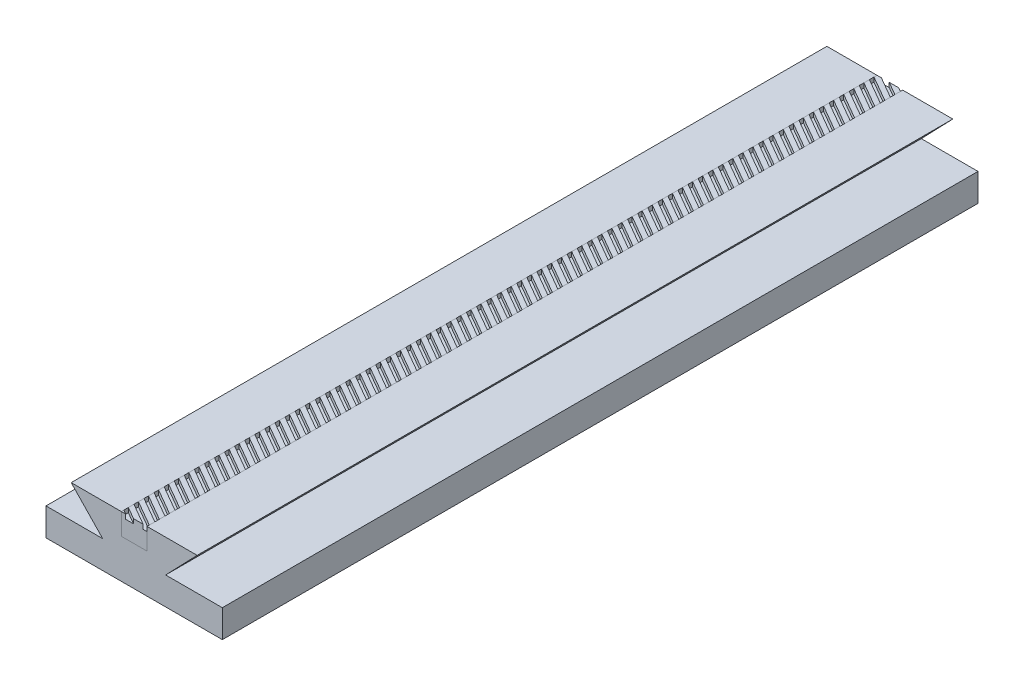
SolidWorks part; units mm, degrees
material "6061"
ref_plane "前视基准面" through (0, 0, 0) normal (0, 0, 1) x (1, 0, 0)
ref_plane "上视基准面" through (0, 0, 0) normal (0, 1, 0) x (1, 0, 0)
ref_plane "右视基准面" through (0, 0, 0) normal (1, 0, 0) x (0, 0, -1)
sketch "草图1" plane through (0, 0, 0) normal (0, 0, 1) x (1, 0, 0)
  line L0 (0, -419.1211) -> (0, 20536.9346) construction
  line L1 (35, 0) -> (-35, 0)
  line L2 (-35, 0) -> (-35, 11)
  line L3 (-35, 11) -> (-12.5, 11)
  line L4 (25, 24) -> (-25, 24)
  line L5 (-25, 24) -> (-12.5, 11)
  line L6 (25, 24) -> (12.5, 11)
  line L7 (35, 11) -> (12.5, 11)
  line L8 (35, 0) -> (35, 11)
  point P12 (0, 24)
  point P14 (0, 0)
  dimension "D1" = 70
  dimension "D2" = 11
  dimension "D3" = 24
  dimension "D4" = 25
  dimension "D5" = 50
extrude "凸台-拉伸1" add sketch "草图1" along normal mid plane 300
sketch "草图2" plane through (0, 0, 150) normal (0, 0, 1) x (1, 0, 0)
  line L0 (25, 24) -> (-25, 24) construction
  line L1 (-5.1, 15.5) -> (-5.1, 24)
  line L2 (5.1, 15.5) -> (5.1, 24)
  line L3 (5.1, 15.5) -> (-5.1, 15.5)
  line L5 (0, 24) -> (-5.1, 15.5) construction
  line L6 (5.1, 15.5) -> (0, 24) construction
  line L7 (0, 0) -> (0, 24.3041) construction
  point P0 (0, 24)
  dimension "D1" = 8.5
  dimension "D2" = 10.2
extrude "切除-拉伸1" cut sketch "草图2" against normal through all and the other way through all
sketch "草图3" plane through (0, 0, 150) normal (0, 0, 1) x (1, 0, 0)
  line L1 (-5.1, 24) -> (5.1, 24)
  line L2 (-5.1, 24) -> (-5.1, 15.5)
  line L3 (-5.1, 15.5) -> (5.1, 15.5)
  line L4 (5.1, 24) -> (5.1, 15.5)
extrude "凸台-拉伸2" add sketch "草图3" against normal up to surface (300 mm away) separate body up to face at (0, 14.25, -150)
sketch "草图4" plane through (0, 24, 0) normal (0, 1, 0) x (1, 0, 0)
  line L0 (-5.1, 156.8) -> (5.1, 150.911)
  line L1 (-5.1, 150) -> (-5.1, -150) construction
  line L2 (5.1, -150) -> (5.1, 150) construction
  line L3 (5.1, 150.911) -> (5.1, 149.111)
  line L4 (5.1, 150) -> (5.1, -150) construction
  line L5 (5.1, 149.111) -> (-5.1, 155)
  line L6 (-5.1, 155) -> (-5.1, 156.8)
  dimension "D1" = 1.8
  dimension "D2" = 120
  dimension "D3" = 5
extrude "切除-拉伸2" cut sketch "草图4" against normal blind 1.8
pattern_linear "阵列(线性)1" count 78 spacing 4 along (0, 0, 1) of "切除-拉伸2"
hole_wizard "打孔尺寸(%根据)内六角圆柱头螺钉的类型1" positions "草图6" profile "草图5" counterbore size "M4" standard "GB"
sketch "草图6" plane through (0, 0, 0) normal (0, -1, 0) x (-1, 0, 0)
  line L0 (35, 150) -> (-35, 150) construction
  line L1 (35, -150) -> (-35, -150) construction
  point P0 (0, 115)
  point P2 (0, 0)
  point P4 (0, -115)
  dimension "D1" = 35
  dimension "D2" = 35
  dimension "D3" = 115
sketch "草图5" plane through (0, 0, -115) normal (1, 0, 0) x (0, 0, -1)
  line L0 (0, 0) -> (0, 16.8519)
  line L1 (0, 16.8519) -> (2.25, 15.5)
  line L2 (2.25, 15.5) -> (2.25, 4.6)
  line L3 (2.25, 4.6) -> (4, 4.6)
  line L4 (4, 4.6) -> (4, 0)
  line L5 (4, 0) -> (0, 0)
  line L10 (0, 16.8519) -> (-2.25, 15.5) construction
  line L11 (0, -6.35) -> (0, 107.95) construction
  dimension "孔直径" = 4.5
  dimension "孔深度" = 15.5
  dimension "柱形沉头孔直径" = 8
  dimension "柱形沉头孔深度" = 4.6
  dimension "导头角度" = 118
hole_wizard "M5 螺纹孔1" positions "草图8" profile "草图7" tap size "M5" standard "GB"
sketch "草图8" plane through (0, 0, -150) normal (0, 0, -1) x (-1, 0, 0)
  line L1 (35, 0) -> (-35, 0) construction
  point P0 (-25, 5)
  point P2 (0, 5)
  point P4 (25, 5)
  dimension "D1" = 50
  dimension "D2" = 25
  dimension "D3" = 5
sketch "草图7" plane through (25, 5, -150) normal (1, 0, 0) x (0, 1, 0)
  line L0 (0, 0) -> (0, 13.6618)
  line L1 (0, 13.6618) -> (2.1, 12.4)
  line L2 (2.1, 12.4) -> (2.1, 0)
  line L5 (2.1, 0) -> (0, 0)
  line L10 (0, 13.6618) -> (-2.1, 12.4) construction
  line L11 (0, -6.35) -> (0, 107.95) construction
  dimension "螺纹孔钻头直径" = 4.2
  dimension "螺纹孔钻头深度" = 12.4
  dimension "导头角度" = 118
cosmetic thread "孔螺蚊线1" parameters "D1"=10, "D2"=5
cosmetic thread "孔螺蚊线2" parameters "D1"=10, "D2"=5
cosmetic thread "孔螺蚊线3" parameters "D1"=10, "D2"=5
